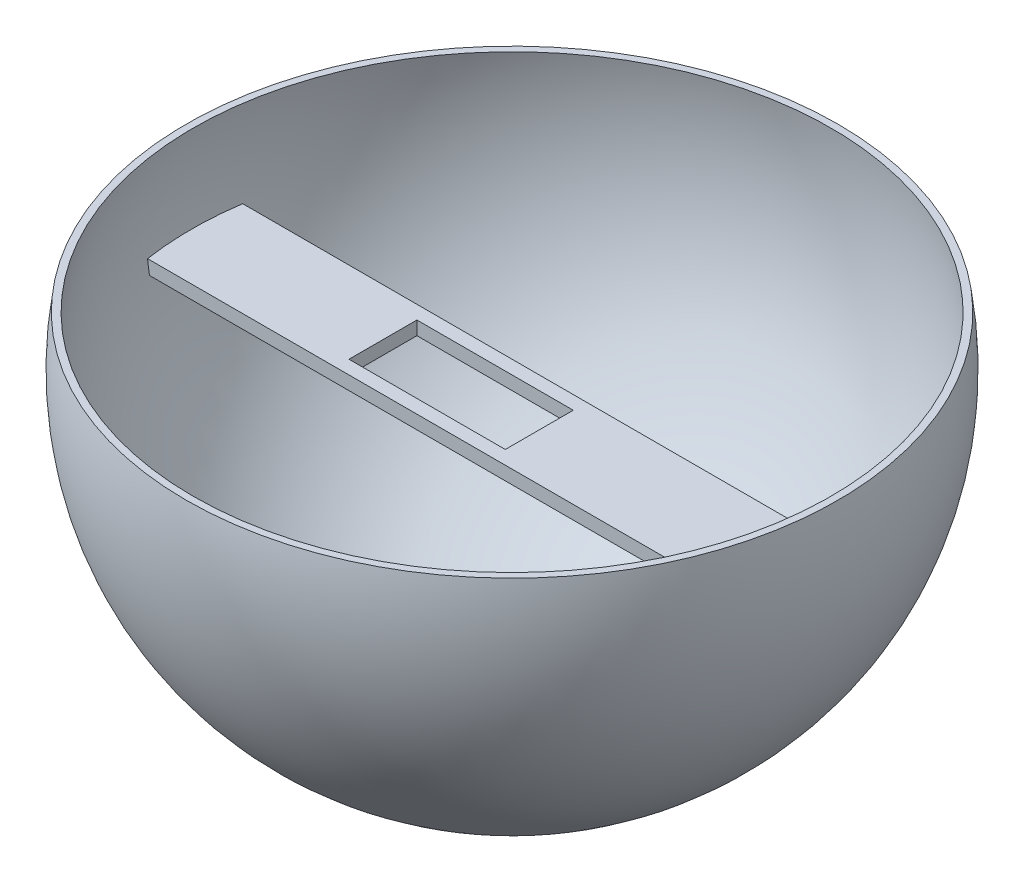
SolidWorks part; units mm, degrees
ref_plane "前视基准面" through (0, 0, 0) normal (0, 0, 1) x (1, 0, 0)
ref_plane "上视基准面" through (0, 0, 0) normal (0, 1, 0) x (1, 0, 0)
ref_plane "右视基准面" through (0, 0, 0) normal (1, 0, 0) x (0, 0, -1)
sketch "草图1" plane through (0, 0, 0) normal (1, 0, 0) x (0, 0, -1)
  line L0 (-47.9421, 7.3351) -> (0, 7.3351)
  line L1 (0, 7.3351) -> (0, -48.5)
  arc A0 (-47.9421, 7.3351) -> (0, -48.5) centre (0, 0) ccw
  dimension "D1" = 97
revolve "旋转1" add sketch "草图1" angle 360 about L1
shell "抽壳1" thickness 1 removed face at (0, 7.3351, 47.9421)
ref_plane "基准面1" through (0, -7.6649, 0) normal (0, 1, 0) x (1, 0, 0)
sketch "草图3" plane through (0, 0, 0) normal (1, 0, 0) x (0, 0, -1)
  line L0 (52.7363, -7.6649) -> (-52.7363, -7.6649) construction
  line L1 (7, -5.6649) -> (-7, -5.6649)
  line L2 (7, -5.6649) -> (7, -7.6649)
  line L3 (7, -7.6649) -> (-7, -7.6649)
  line L4 (-7, -5.6649) -> (-7, -7.6649)
  dimension "D1" = 2
  dimension "D2" = 7
  dimension "D3" = 7
extrude "凸台-拉伸1" add sketch "草图3" along normal up to next
sketch "草图4" plane through (0, 0, 0) normal (1, 0, 0) x (0, 0, -1)
  line L1 (-7, -5.6649) -> (7, -5.6649)
  line L2 (-7, -5.6649) -> (-7, -7.6649)
  line L3 (-7, -7.6649) -> (7, -7.6649)
  line L4 (7, -5.6649) -> (7, -7.6649)
extrude "凸台-拉伸2" add sketch "草图4" against normal up to next
sketch "草图5" plane through (0, -7.6649, 0) normal (0, 1, 0) x (1, 0, 0)
  line L1 (4, -5) -> (-19, -5)
  line L2 (4, -5) -> (4, 5)
  line L3 (4, 5) -> (-19, 5)
  line L4 (-19, -5) -> (-19, 5)
  line L5 (-1.1553, -5) -> (-1.1553, -7) construction
  line L6 (46.3519, -7) -> (-46.3519, -7) construction
  line L7 (-2.4162, 5) -> (-2.4162, 7) construction
  line L8 (46.3519, 7) -> (-46.3519, 7) construction
  dimension "D1" = 10
  dimension "D2" = 23
  dimension "D3" = 4
extrude "切除-拉伸2" cut sketch "草图5" along normal blind 5 contours L1 L4 L3 L2
